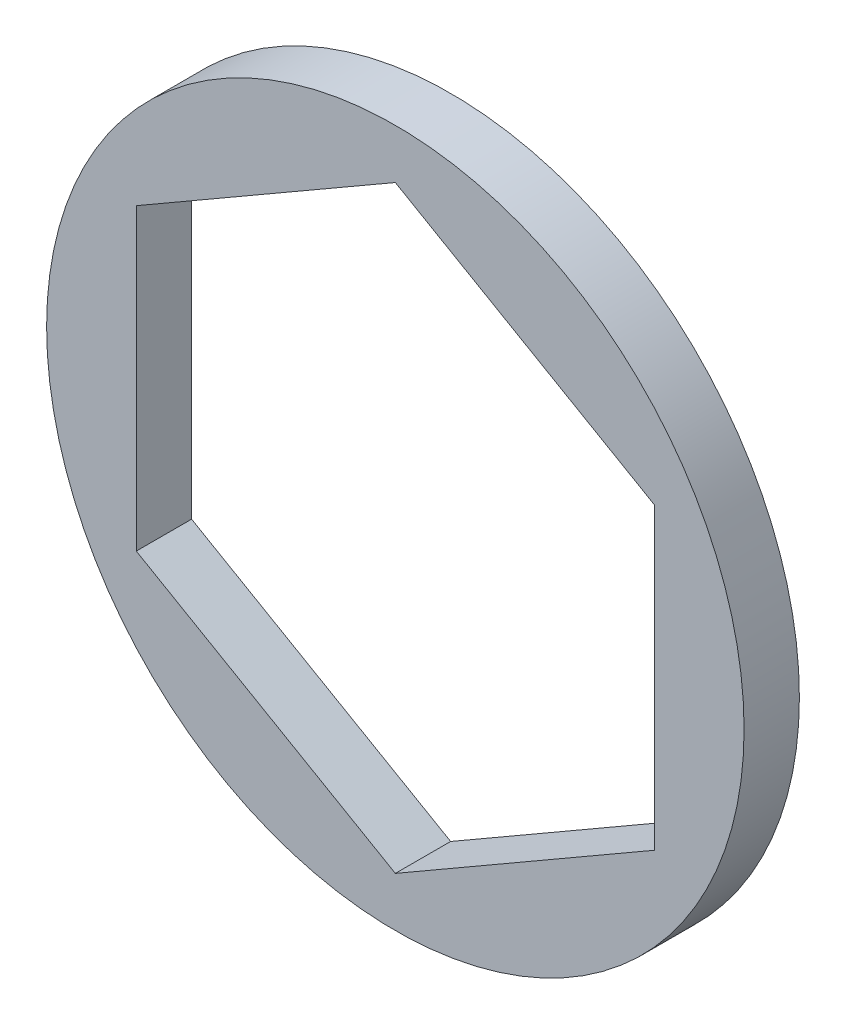
SolidWorks part; units mm, degrees
material "Nylon 101"
ref_plane "Front Plane" through (0, 0, 0) normal (0, 0, 1) x (1, 0, 0)
ref_plane "Top Plane" through (0, 0, 0) normal (0, 1, 0) x (1, 0, 0)
ref_plane "Right Plane" through (0, 0, 0) normal (1, 0, 0) x (0, 0, -1)
sketch "Sketch1" plane through (0, 0, 0) normal (0, 0, 1) x (1, 0, 0)
  line L1 (6.604, 3.8128) -> (0, 7.6256)
  line L2 (0, 7.6256) -> (-6.604, 3.8128)
  line L3 (-6.604, 3.8128) -> (-6.604, -3.8128)
  line L4 (-6.604, -3.8128) -> (0, -7.6256)
  line L5 (0, -7.6256) -> (6.604, -3.8128)
  line L6 (6.604, -3.8128) -> (6.604, 3.8128)
  circle A0 centre (0, 0) radius 6.604 construction
  circle A1 centre (0, 0) radius 8.89
  dimension "D1" = 13.208
  dimension "D2" = 17.78
extrude "Boss-Extrude1" add sketch "Sketch1" along normal blind 1.4097
